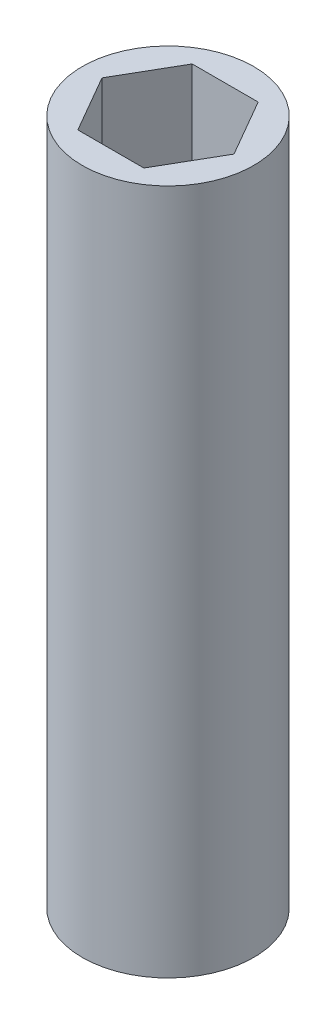
SolidWorks part; units mm, degrees
material "PET"
ref_plane "Front" through (0, 0, 0) normal (0, 0, 1) x (1, 0, 0)
ref_plane "Top" through (0, 0, 0) normal (0, 1, 0) x (1, 0, 0)
ref_plane "Right" through (0, 0, 0) normal (1, 0, 0) x (0, 0, -1)
sketch "Sketch1" plane through (0, 0, 0) normal (0, 1, 0) x (1, 0, 0)
  line L1 (3.6662, 6.35) -> (-3.6662, 6.35)
  line L2 (-3.6662, 6.35) -> (-7.3323, 0)
  line L3 (-7.3323, 0) -> (-3.6662, -6.35)
  line L4 (-3.6662, -6.35) -> (3.6662, -6.35)
  line L5 (3.6662, -6.35) -> (7.3323, 0)
  line L6 (7.3323, 0) -> (3.6662, 6.35)
  circle A0 centre (0, 0) radius 9.525
  circle A1 centre (0, 0) radius 6.35 construction
  dimension "D2" = 19.05
  dimension "D1" = 12.7
extrude "Boss-Extrude1" add sketch "Sketch1" along normal blind 76.2
